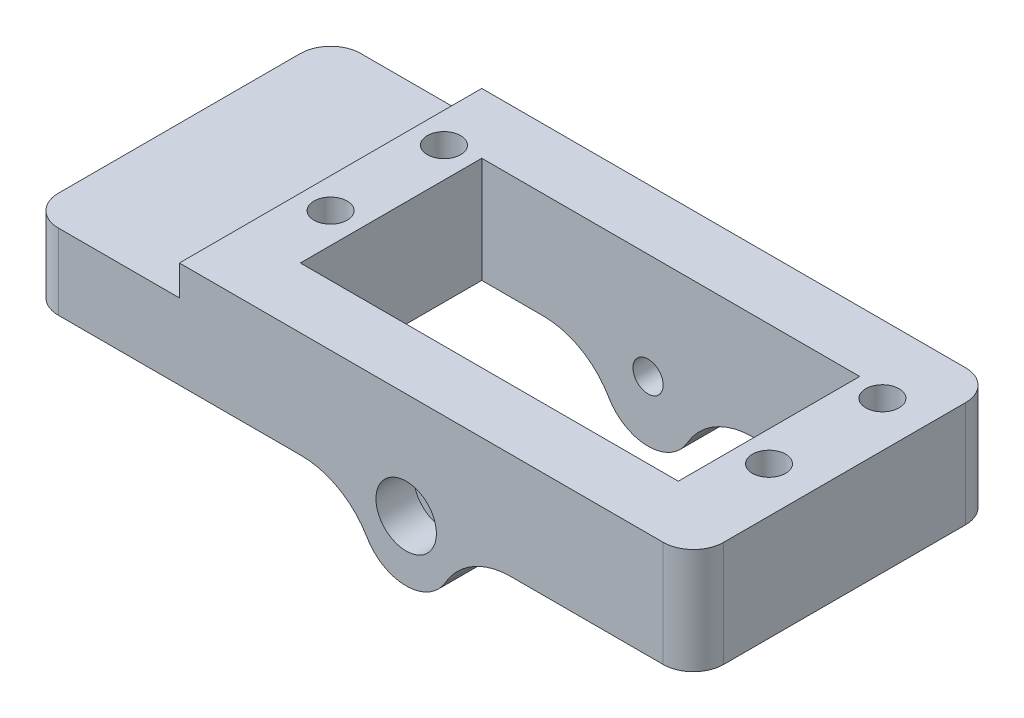
SolidWorks part; units mm, degrees
ref_plane "前视基准面" through (0, 0, 0) normal (0, 0, 1) x (1, 0, 0)
ref_plane "上视基准面" through (0, 0, 0) normal (0, 1, 0) x (1, 0, 0)
ref_plane "右视基准面" through (0, 0, 0) normal (1, 0, 0) x (0, 0, -1)
sketch "草图1" plane through (0, 0, 0) normal (0, 1, 0) x (1, 0, 0)
  line L1 (-25, -10) -> (25, -10)
  line L2 (-25, -10) -> (-25, 10)
  line L3 (-25, 10) -> (25, 10)
  line L4 (25, -10) -> (25, 10)
  line L5 (-25, -10) -> (25, 10) construction
  line L6 (-25, 10) -> (25, -10) construction
  point P0 (0, 0)
  dimension "D1" = 20
  dimension "D2" = 50
extrude "凸台-拉伸1" add sketch "草图1" along normal blind 7
sketch "草图2" plane through (0, 0, 10) normal (0, 0, 1) x (1, 0, 0)
  line L0 (-25, 0) -> (25, 0) construction
  line L3 (-25, 7) -> (-25, 0) construction
  line L4 (0, -0.7454) -> (0, 2.7804) construction
  line L8 (-25, 0) -> (25, 0)
  line L9 (25, 0) -> (25, 7)
  line L10 (25, 7) -> (-25, 7)
  line L11 (-25, 7) -> (-25, 0)
  line L12 (-2.8284, 0) -> (2.8284, 0)
  arc A0 (-2.8284, 0) -> (2.8284, 0) centre (0, -1) ccw
  dimension "D1" = 3
  dimension "D2" = 25
  dimension "D4" = 1
  dimension "D3" = 0
extrude "凸台-拉伸2" add sketch "草图2" against normal blind 5
sketch "草图3" plane through (0, 0, 10) normal (0, 0, 1) x (1, 0, 0)
  line L0 (0, -200000.7454) -> (0, 200002.7804) construction
  line L1 (-25, 7) -> (25, 7) construction
  circle A0 centre (0, 0) radius 1
  dimension "D1" = 2
  dimension "D2" = 7
extrude "切除-拉伸1" cut sketch "草图3" against normal through all
mirror "镜向1" about plane through (0, 0, 0) normal (0, 0, 1) of "切除-拉伸1", "凸台-拉伸2"
sketch "草图5" plane through (0, 7, 0) normal (0, 1, 0) x (1, 0, 0)
  line L0 (-6.05, 0) -> (6.05, 0) construction
  line L1 (25, 10) -> (19, 10)
  line L2 (25, 10) -> (25, -10)
  line L3 (25, -10) -> (19, -10)
  line L4 (19, 10) -> (19, -10)
  line L5 (25, 10) -> (19, -10) construction
  line L6 (25, -10) -> (19, 10) construction
  line L7 (-25, -10) -> (25, -10) construction
  line L8 (25, -10) -> (25, 10) construction
  point P0 (22, 0)
  dimension "D1" = 6
extrude "切除-拉伸5" cut sketch "草图5" against normal through all
sketch "草图6" plane through (0, 0, 10) normal (0, 0, 1) x (1, 0, 0)
  circle A0 centre (0, 0) radius 2
  dimension "D1" = 4
extrude "切除-拉伸6" cut sketch "草图6" against normal blind 2.5
fillet "圆角2" radius 2 4 edges at (-25, 3.5, -10) (-25, 3.5, 10) (19, 3.5, 10) (19, 3.5, -10)
fillet "圆角3" radius 5 4 edges at (-2.8284, 0, 7.5) (2.8284, 0, 7.5) (2.8284, 0, -7.5) (-2.8284, 0, -7.5)
sketch "草图8" plane through (0, 7, 0) normal (0, 1, 0) x (1, 0, 0)
  line L0 (17, 10) -> (-23, 10) construction
  line L2 (-25, 8) -> (-25, -8) construction
  circle A0 centre (-13, 5.5) radius 1.1
  circle A1 centre (-13, -2) radius 1.1
  circle A2 centre (16, 5.5) radius 1.1
  circle A3 centre (16, -2) radius 1.1
  dimension "D1" = 2.2
  dimension "D2" = 4.5
  dimension "D3" = 12
  dimension "D4" = 7.5
  dimension "D5" = 29
  dimension "D6" = 7.5
extrude "切除-拉伸9" cut sketch "草图8" against normal through all
sketch "草图7" plane through (0, 7, 0) normal (0, 1, 0) x (1, 0, 0)
  line L0 (-6.05, 0) -> (6.05, 0) construction
  line L2 (-11, 6) -> (14, 6)
  line L3 (-11, 6) -> (-11, -6)
  line L4 (-11, -6) -> (14, -6)
  line L5 (14, 6) -> (14, -6)
  line L6 (-11, 6) -> (14, -6) construction
  line L7 (-11, -6) -> (14, 6) construction
  line L8 (19, 8) -> (19, -8) construction
  point P2 (1.5, 0)
  dimension "D1" = 12
  dimension "D2" = 5
  dimension "D3" = 25
extrude "切除-拉伸7" cut sketch "草图7" against normal through all
sketch "草图10" plane through (0, 0, 0) normal (0, -1, 0) x (1, 0, 0)
  line L0 (6.05, 0) -> (-6.05, 0) construction
  line L1 (-25, -8) -> (-25, 8) construction
  circle A0 centre (-20, 0) radius 3
  dimension "D1" = 6
  dimension "D2" = 5
extrude "切除-拉伸11" cut sketch "草图10" against normal blind 3
sketch "草图12" plane through (0, 3, 0) normal (0, -1, 0) x (1, 0, 0)
  circle A0 centre (-20, 0) radius 2
  dimension "D1" = 4
extrude "凸台-拉伸3" add sketch "草图12" along normal blind 5
sketch "草图13" plane through (0, 7, 0) normal (0, 1, 0) x (1, 0, 0)
  line L0 (-23, -10) -> (17, -10) construction
  line L1 (-15, 10) -> (-25, 10)
  line L2 (-15, 10) -> (-15, -10)
  line L3 (-15, -10) -> (-25, -10)
  line L4 (-25, 10) -> (-25, -10)
  line L5 (-25, 8) -> (-25, -8) construction
  line L6 (17, 10) -> (-23, 10) construction
  dimension "D1" = 10
extrude "切除-拉伸12" cut sketch "草图13" against normal blind 2
